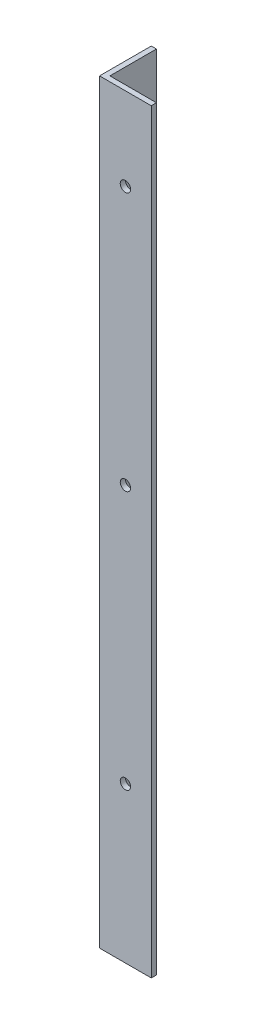
SolidWorks part; units mm, degrees
material "1060 Alloy"
ref_plane "Front Plane" through (0, 0, 0) normal (0, 0, 1) x (1, 0, 0)
ref_plane "Top Plane" through (0, 0, 0) normal (0, 1, 0) x (1, 0, 0)
ref_plane "Right Plane" through (0, 0, 0) normal (1, 0, 0) x (0, 0, -1)
sketch "Sketch1" plane through (0, 0, 0) normal (0, 1, 0) x (1, 0, 0)
  line L1 (0, 0) -> (20, 0)
  line L2 (0, 0) -> (0, 20)
  line L3 (0, 20) -> (2, 20)
  line L4 (20, 0) -> (20, 2)
  line L7 (20, 2) -> (2, 2)
  line L8 (2, 20) -> (2, 2)
  dimension "D1" = 20
  dimension "D2" = 20
  dimension "D3" = 2
  dimension "D4" = 2
extrude "Boss-Extrude1" add sketch "Sketch1" along normal blind 146 and the other way blind 146
sketch "Sketch2" plane through (0, 0, 0) normal (0, 0, 1) x (1, 0, 0)
  line L0 (10, 146) -> (10, -146) construction
  line L1 (0, 146) -> (20, 146) construction
  line L2 (0, -146) -> (20, -146) construction
  line L3 (0, -146) -> (0, 146) construction
  circle A0 centre (10, 114) radius 2
  circle A1 centre (10, 14) radius 2
  circle A2 centre (10, -86) radius 2
  dimension "D1" = 4
  dimension "D2" = 4
  dimension "D3" = 4
  dimension "D4" = 100
  dimension "D5" = 100
  dimension "D6" = 60
  dimension "D7" = 10
extrude "Cut-Extrude1" cut sketch "Sketch2" against normal blind 10
sketch "Sketch3" plane through (0, 0, 0) normal (-1, 0, 0) x (0, 0, 1)
  line L0 (-8, -146) -> (-8, 146) construction
  line L1 (-20, -146) -> (0, -146) construction
  line L2 (-20, 146) -> (0, 146) construction
  line L3 (0, -146) -> (0, 146) construction
  circle A0 centre (-8, -114) radius 2
  circle A1 centre (-8, -14) radius 2
  circle A2 centre (-8, 86) radius 2
  dimension "D3" = 4
  dimension "D4" = 4
  dimension "D5" = 4
  dimension "D1" = 100
  dimension "D2" = 100
  dimension "D6" = 60
  dimension "D7" = 8
extrude "Cut-Extrude2" cut sketch "Sketch3" against normal blind 10
